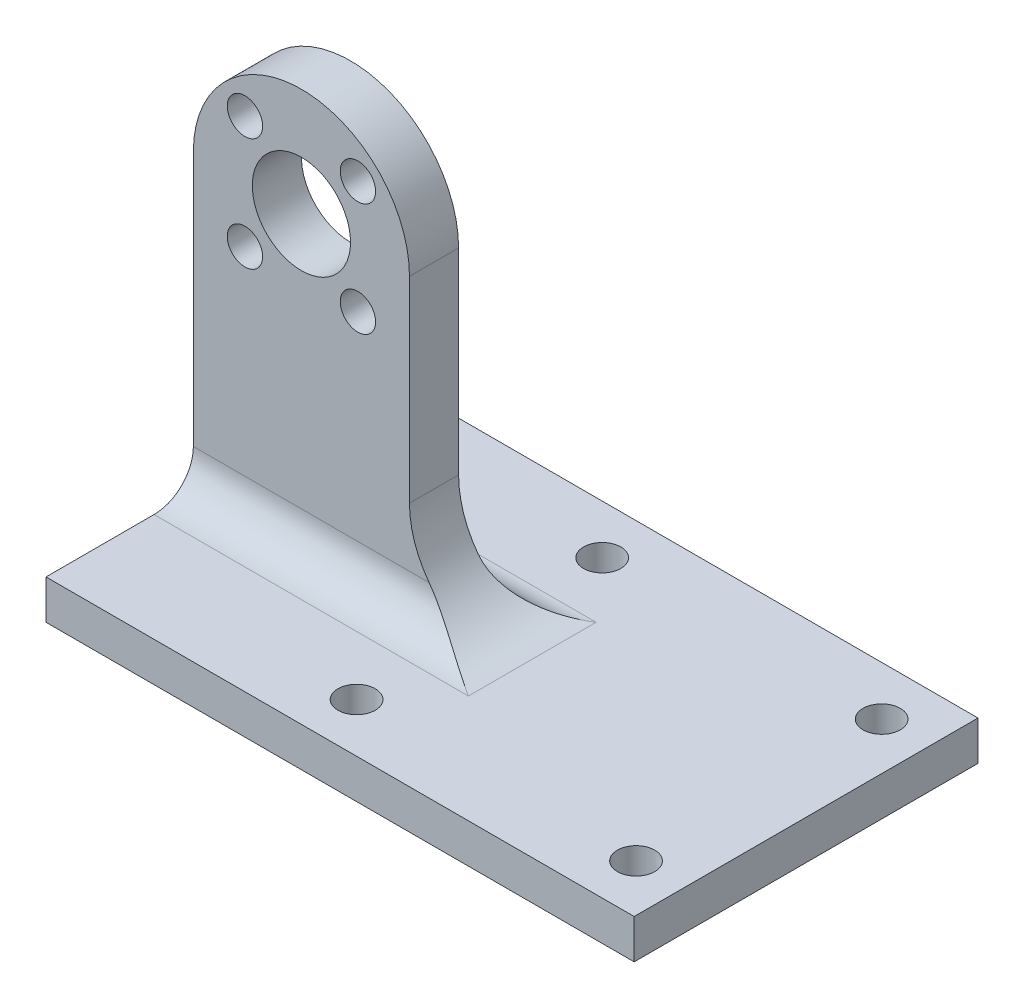
SolidWorks part; units mm, degrees
ref_plane "Front Plane" through (0, 0, 0) normal (0, 0, 1) x (1, 0, 0)
ref_plane "Top Plane" through (0, 0, 0) normal (0, 1, 0) x (1, 0, 0)
ref_plane "Right Plane" through (0, 0, 0) normal (1, 0, 0) x (0, 0, -1)
sketch "Sketch1" plane through (0, 0, 0) normal (0, 0, 1) x (1, 0, 0)
  line L1 (-5.75, 5.75) -> (5.75, 5.75) construction
  line L2 (-5.75, 5.75) -> (-5.75, -5.75) construction
  line L3 (-5.75, -5.75) -> (5.75, -5.75) construction
  line L4 (5.75, 5.75) -> (5.75, -5.75) construction
  line L5 (-5.75, 5.75) -> (5.75, -5.75) construction
  line L6 (-5.75, -5.75) -> (5.75, 5.75) construction
  circle A0 centre (-5.75, 5.75) radius 1.8
  circle A1 centre (5.75, 5.75) radius 1.8
  circle A2 centre (5.75, -5.75) radius 1.8
  circle A3 centre (-5.75, -5.75) radius 1.8
  circle A4 centre (0, 0) radius 11
  point P0 (0, 0)
  dimension "D1" = 3.6
  dimension "D3" = 22
  dimension "D2" = 11.5
extrude "Boss-Extrude1" add sketch "Sketch1" along normal blind 5
sketch "Sketch2" plane through (0, 0, 0) normal (0, 0, -1) x (-1, 0, 0)
  line L0 (-11, 0) -> (-11, -30)
  line L1 (-11, -30) -> (11, -30)
  line L2 (11, -30) -> (11, 0)
  arc A0 (-11, 0) -> (11, 0) centre (0, 0) ccw
  circle A1 centre (0, 0) radius 11 construction
  point P6 (0, -11)
  circle M1 centre (0, 0) radius 11
  dimension "D1" = 19
extrude "Boss-Extrude2" add sketch "Sketch2" against normal up to surface (5 mm away) contours L0 L1 M1 | L1 L2 M1 region at (0, -19.1786, 0) up to face at (7.55, -5.75, 5)
sketch "Sketch3" plane through (0, -30, 0) normal (0, -1, 0) x (1, 0, 0)
  line L0 (10.6144, -15) -> (-11, -15)
  line L16 (10.6144, -15) -> (20.6144, -15)
  line L17 (20.6144, -15) -> (20.6144, 20) construction
  line L18 (20.6144, 20) -> (10.6144, 20)
  line L22 (0, 2.5) -> (6.1746, 2.5) construction
  line L23 (15.6144, -15) -> (15.6144, -10) construction
  line L24 (-11, -15) -> (-11, 20)
  line L25 (-11, 20) -> (10.6144, 20)
  line L26 (-11, 5) -> (-11, 0) construction
  line L27 (20.6144, -15) -> (48.8735, -15)
  line L28 (48.8735, -15) -> (48.8735, 20)
  line L29 (48.8735, 20) -> (20.6144, 20)
  circle A4 centre (15.6144, -10) radius 1.9
  circle A5 centre (15.6144, 15) radius 1.9
  circle A8 centre (44.0649, 15) radius 1.9
  circle A9 centre (44.0649, -10) radius 1.9
  point P5 (0, 2.5)
  dimension "D4" = 5
  dimension "D5" = 3.8
extrude "Boss-Extrude3" add sketch "Sketch3" along normal blind 4
fillet "Fillet2" radius 10 1 edges at (11, -30, 2.5)
sketch "Sketch4" plane through (0, 0, 5) normal (0, 0, 1) x (1, 0, 0)
  circle A0 centre (0, 0) radius 5
  dimension "D1" = 10
extrude "Cut-Extrude1" cut sketch "Sketch4" against normal blind 10
fillet "Fillet3" radius 4 2 edges at (5, -30, 0) (5, -30, 5)
